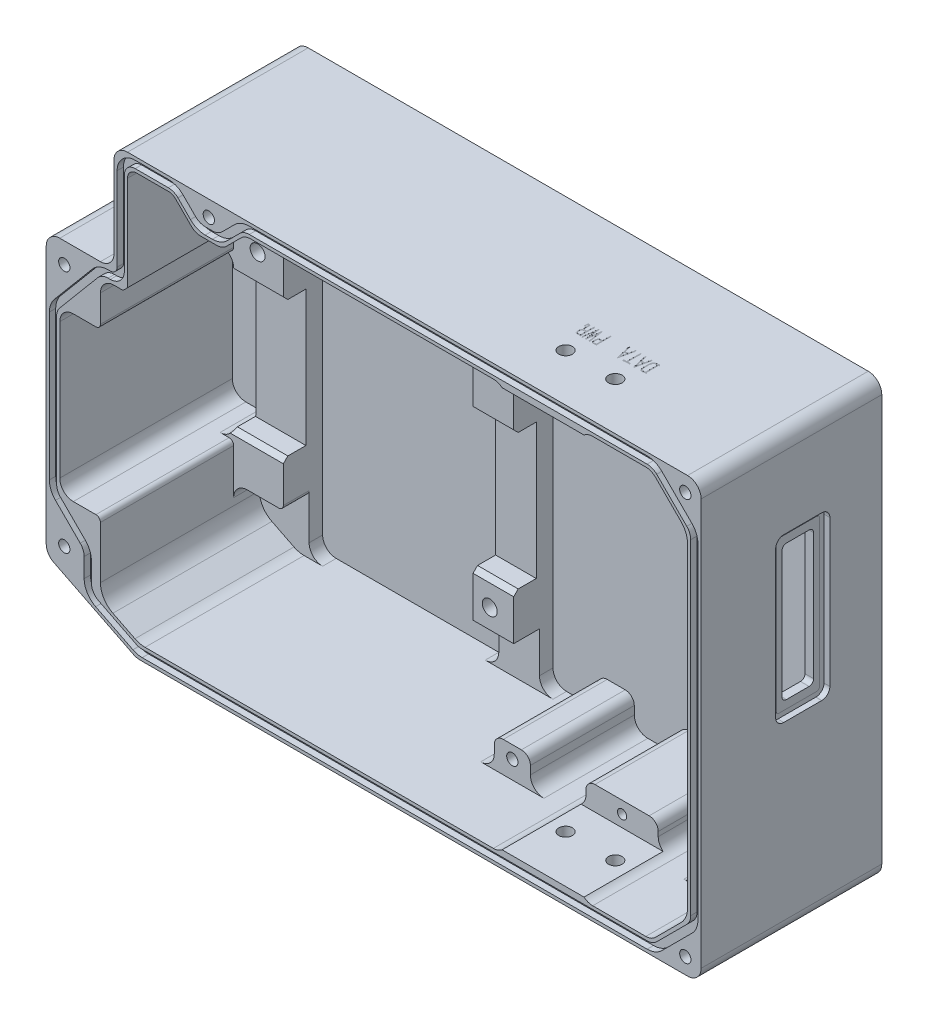
SolidWorks part; units mm, degrees
material "6061 合金"
ref_plane "前视基准面" through (0, 0, 0) normal (0, 0, 1) x (1, 0, 0)
ref_plane "上视基准面" through (0, 0, 0) normal (0, 1, 0) x (1, 0, 0)
ref_plane "右视基准面" through (0, 0, 0) normal (1, 0, 0) x (0, 0, -1)
sketch "草图1" plane through (0, 0, 0) normal (0, 0, 1) x (1, 0, 0)
  line L0 (15, 96) -> (15, 72)
  line L1 (20, 0) -> (145, 0)
  line L2 (0, 10) -> (0, 72)
  line L3 (15, 96) -> (145, 96)
  line L4 (145, 0) -> (145, 96)
  line L5 (0, 10) -> (20, 0)
  line L6 (15, 72) -> (0, 72)
  dimension "D1" = 125
  dimension "D2" = 96
  dimension "D3" = 130
  dimension "D4" = 10
  dimension "D5" = 24
  dimension "D6" = 145
extrude "凸台-拉伸1" add sketch "草图1" along normal blind 40
sketch "草图2" plane through (0, 0, 40) normal (0, 0, 1) x (1, 0, 0)
  line L5 (18, 93) -> (18, 69)
  line L6 (18, 93) -> (18, 69)
  line L8 (3, 69) -> (3, 11.8541)
  line L9 (20.7082, 3) -> (142, 3)
  line L10 (142, 3) -> (142, 93)
  line L11 (142, 93) -> (18, 93)
  line L12 (3, 69) -> (3, 11.8541)
  line L13 (20.7082, 3) -> (142, 3)
  line L14 (142, 3) -> (142, 93)
  line L15 (142, 93) -> (18, 93)
  line L16 (3, 11.8541) -> (20.7082, 3)
  line L17 (3, 11.8541) -> (20.7082, 3)
  line L19 (18, 69) -> (3, 69)
  line L20 (18, 69) -> (3, 69)
  dimension "D1" = 3
extrude "切除-拉伸1" cut sketch "草图2" against normal offset from surface (38.2 mm away) 1.8 up to face at (48.5714, 49.4286, 0)
sketch "草图74" plane through (0, 0, 1.8) normal (0, 0, 1) x (1, 0, 0)
  line L0 (18, 93) -> (18, 69) construction
  line L1 (18, 81) -> (74, 81)
  line L2 (18, 81) -> (18, 61)
  line L3 (18, 61) -> (74, 61)
  line L4 (74, 81) -> (74, 61)
  line L6 (145, 96) -> (15, 96) construction
  line L7 (145, 0) -> (145, 96) construction
  dimension "D1" = 15
  dimension "D2" = 20
  dimension "D3" = 71
extrude "凸台-拉伸25" add sketch "草图74" along normal blind 3
sketch "草图70" plane through (0, 0, 1.8) normal (0, 0, 1) x (1, 0, 0)
  line L1 (28, 93) -> (44, 93)
  line L5 (33, 88) -> (39, 88)
  line L6 (39, 88) -> (44, 93)
  line L7 (142, 93) -> (18, 93) construction
  line L8 (33, 88) -> (28, 93)
  line L9 (142, 93) -> (18, 93) construction
  line L10 (18, 93) -> (18, 81) construction
  dimension "D1" = 45
  dimension "D2" = 45
  dimension "D3" = 10
  dimension "D4" = 5
  dimension "D5" = 16
extrude "凸台-拉伸24" add sketch "草图70" along normal up to surface (38.2 mm away) up to face at (49.5297, 48.8363, 40)
sketch "草图39" plane through (0, 0, 1.8) normal (0, 0, 1) x (1, 0, 0)
  line L0 (134, 93) -> (142, 85)
  line L3 (142, 85) -> (142, 93)
  line L4 (142, 93) -> (134, 93)
  line L5 (134, 3) -> (142, 3)
  line L7 (142, 3) -> (142, 11)
  line L8 (142, 3) -> (142, 93) construction
  line L9 (142, 11) -> (134, 3)
  dimension "D1" = 8
  dimension "D2" = 8
  dimension "D3" = 8
  dimension "D4" = 8
extrude "凸台-拉伸9" add sketch "草图39" along normal up to surface (38.2 mm away) up to face at (44.6098, 63.9867, 40)
fillet "圆角66" radius 3 1 edges at (15, 72, 20)
fillet "圆角17" radius 3 2 edges at (145, 96, 20) (145, 0, 20)
sketch "草图17" plane through (145, 0, 0) normal (1, 0, 0) x (0, 0, -1)
  line L0 (-40, 3) -> (-40, 93) construction
  line L1 (-20, 74) -> (-15, 74)
  line L2 (-21, 73) -> (-21, 45)
  line L3 (-20, 44) -> (-15, 44)
  line L4 (-14, 73) -> (-14, 45)
  line L5 (-40, 96) -> (0, 96) construction
  arc A0 (-21, 45) -> (-20, 44) centre (-20, 45) ccw
  arc A1 (-15, 44) -> (-14, 45) centre (-15, 45) ccw
  arc A2 (-14, 73) -> (-15, 74) centre (-15, 73) ccw
  arc A3 (-21, 73) -> (-20, 74) centre (-20, 73) cw
  point P10 (-21, 44)
  point P15 (-14, 74)
  point P18 (-21, 74)
  dimension "D5" = 1
  dimension "D1" = 7
  dimension "D2" = 19
  dimension "D3" = 22
  dimension "D4" = 30
extrude "切除-拉伸2" cut sketch "草图17" against normal blind 10
sketch "草图18" plane through (0, 0, 0) normal (0, 0, -1) x (-1, 0, 0)
  line L0 (-142, 96) -> (-15, 96) construction
  line L1 (-63, 74) -> (-35, 74)
  line L2 (-64, 73) -> (-64, 68)
  line L3 (-63, 67) -> (-35, 67)
  line L4 (-34, 73) -> (-34, 68)
  line L5 (-145, 3) -> (-145, 93) construction
  arc A0 (-34, 73) -> (-35, 74) centre (-35, 73) ccw
  arc A1 (-34, 68) -> (-35, 67) centre (-35, 68) cw
  arc A2 (-64, 68) -> (-63, 67) centre (-63, 68) ccw
  arc A3 (-64, 73) -> (-63, 74) centre (-63, 73) cw
  point P10 (-34, 74)
  point P15 (-64, 67)
  point P18 (-64, 74)
  dimension "D5" = 1
  dimension "D1" = 7
  dimension "D2" = 30
  dimension "D3" = 22
  dimension "D4" = 81
extrude "切除-拉伸3" cut sketch "草图18" against normal blind 10
sketch "草图19" plane through (145, 0, 0) normal (1, 0, 0) x (0, 0, -1)
  line L5 (-21.7, 77) -> (-13.3, 77)
  line L6 (-23.5, 75.2) -> (-23.5, 42.8)
  line L7 (-21.7, 41) -> (-13.3, 41)
  line L8 (-11.5, 75.2) -> (-11.5, 42.8)
  line L10 (-21, 59) -> (-54.4631, 59) construction
  line L11 (-21, 73) -> (-21, 45) construction
  line L14 (-17.5, 44) -> (-17.5, 40.5608) construction
  line L15 (-20, 44) -> (-15, 44) construction
  arc A0 (-23.5, 42.8) -> (-21.7, 41) centre (-21.7, 42.8) ccw
  arc A1 (-11.5, 42.8) -> (-13.3, 41) centre (-13.3, 42.8) cw
  arc A2 (-11.5, 75.2) -> (-13.3, 77) centre (-13.3, 75.2) ccw
  arc A3 (-23.5, 75.2) -> (-21.7, 77) centre (-21.7, 75.2) cw
  point P3 (-23.5, 41)
  point P19 (-11.5, 77)
  point P22 (-23.5, 77)
  dimension "D3" = 1.8
  dimension "D1" = 36
  dimension "D2" = 12
extrude "切除-拉伸4" cut sketch "草图19" against normal blind 1.1
sketch "草图20" plane through (0, 0, 0) normal (0, 0, -1) x (-1, 0, 0)
  line L0 (-49, 74) -> (-49, 89.8189) construction
  line L1 (-65.2, 76.5) -> (-32.8, 76.5)
  line L2 (-67, 74.7) -> (-67, 66.3)
  line L3 (-65.2, 64.5) -> (-32.8, 64.5)
  line L4 (-31, 74.7) -> (-31, 66.3)
  line L5 (-35, 74) -> (-63, 74) construction
  line L6 (-64, 70.5) -> (-139.8388, 70.5) construction
  line L7 (-64, 73) -> (-64, 68) construction
  arc A0 (-32.8, 76.5) -> (-31, 74.7) centre (-32.8, 74.7) cw
  arc A1 (-32.8, 64.5) -> (-31, 66.3) centre (-32.8, 66.3) ccw
  arc A2 (-65.2, 64.5) -> (-67, 66.3) centre (-65.2, 66.3) cw
  arc A3 (-67, 74.7) -> (-65.2, 76.5) centre (-65.2, 74.7) cw
  point P14 (-31, 76.5)
  point P19 (-67, 64.5)
  point P22 (-67, 76.5)
  dimension "D3" = 1.8
  dimension "D1" = 36
  dimension "D2" = 12
extrude "切除-拉伸5" cut sketch "草图20" against normal blind 1.1
sketch "草图21" plane through (143.9, 0, 0) normal (1, 0, 0) x (0, 0, -1)
  line L4 (-21.7, 42.2) -> (-13.3, 42.2)
  line L5 (-12.7, 42.8) -> (-12.7, 75.2)
  line L6 (-13.3, 75.8) -> (-21.7, 75.8)
  line L7 (-22.3, 75.2) -> (-22.3, 42.8)
  line L8 (-21.7, 41) -> (-13.3, 41)
  line L9 (-11.5, 42.8) -> (-11.5, 75.2)
  line L10 (-13.3, 77) -> (-21.7, 77)
  line L11 (-23.5, 75.2) -> (-23.5, 42.8)
  line L12 (-21.7, 41) -> (-13.3, 41)
  line L13 (-11.5, 42.8) -> (-11.5, 75.2)
  line L14 (-13.3, 77) -> (-21.7, 77)
  line L15 (-23.5, 75.2) -> (-23.5, 42.8)
  arc A4 (-13.3, 42.2) -> (-12.7, 42.8) centre (-13.3, 42.8) ccw
  arc A5 (-12.7, 75.2) -> (-13.3, 75.8) centre (-13.3, 75.2) ccw
  arc A6 (-21.7, 75.8) -> (-22.3, 75.2) centre (-21.7, 75.2) ccw
  arc A7 (-22.3, 42.8) -> (-21.7, 42.2) centre (-21.7, 42.8) ccw
  arc A8 (-23.5, 42.8) -> (-21.7, 41) centre (-21.7, 42.8) ccw
  arc A9 (-13.3, 41) -> (-11.5, 42.8) centre (-13.3, 42.8) ccw
  arc A10 (-11.5, 75.2) -> (-13.3, 77) centre (-13.3, 75.2) ccw
  arc A11 (-21.7, 77) -> (-23.5, 75.2) centre (-21.7, 75.2) ccw
  arc A12 (-23.5, 42.8) -> (-21.7, 41) centre (-21.7, 42.8) ccw
  arc A13 (-13.3, 41) -> (-11.5, 42.8) centre (-13.3, 42.8) ccw
  arc A14 (-11.5, 75.2) -> (-13.3, 77) centre (-13.3, 75.2) ccw
  arc A15 (-21.7, 77) -> (-23.5, 75.2) centre (-21.7, 75.2) ccw
  dimension "D2" = 1.2
  dimension "D1" = 0
extrude "切除-拉伸9" cut sketch "草图21" against normal blind 0.2
sketch "草图14" plane through (0, 0, 1.8) normal (0, 0, 1) x (1, 0, 0)
  line L0 (3, 69) -> (3, 11.8541) construction
  line L2 (3, 69) -> (3, 59)
  line L3 (3, 59) -> (12, 59)
  line L4 (12, 69) -> (12, 59)
  line L5 (145, 41) -> (0, 41) construction
  line L6 (3, 23) -> (12, 23)
  line L7 (3, 23) -> (3, 11.8541)
  line L8 (3, 11.8541) -> (20.7082, 3) construction
  line L9 (12, 23) -> (12, 7.3541)
  line L11 (3, 69) -> (12, 69)
  line L12 (12, 7.3541) -> (3, 11.8541)
  line L13 (18, 69) -> (3, 69) construction
  line L14 (0, 72) -> (0, 10) construction
  dimension "D1" = 36
  dimension "D2" = 9
  dimension "D3" = 9
extrude "凸台-拉伸11" add sketch "草图14" along normal up to surface (38.2 mm away) up to face at (58.3622, 61.5272, 40)
hole_wizard "M4 螺纹孔1" positions "草图16" profile "草图15" tap size "M4" standard "Iso"
sketch "草图16" plane through (0, 0, 0) normal (-1, 0, 0) x (0, 0, 1)
  line L0 (0, 41) -> (58.2526, 41) construction
  line L1 (0, 72) -> (0, 10) construction
  line L2 (11.5, 63) -> (21.5, 63) construction
  line L4 (11.5, 19) -> (22.5, 19) construction
  point P0 (11.5, 63)
  point P2 (31.5, 63)
  point P4 (31.5, 19)
  point P6 (11.5, 19)
  point P25 (21.5, 63)
  point P27 (21.5, 19)
  dimension "D1" = 44
  dimension "D2" = 44
  dimension "D3" = 11.5
  dimension "D4" = 20
  dimension "D5" = 10
  dimension "D6" = 10
sketch "草图15" plane through (0, 63, 11.5) normal (0, 1, 0) x (0, 0, 1)
  line L0 (0, 0) -> (0, 11.0914)
  line L1 (0, 11.0914) -> (1.65, 10.1)
  line L2 (1.65, 10.1) -> (1.65, 0)
  line L5 (1.65, 0) -> (0, 0)
  line L10 (0, 11.0914) -> (-1.65, 10.1) construction
  line L11 (0, -6.35) -> (0, 107.95) construction
  dimension "螺纹孔钻头直径" = 3.3
  dimension "螺纹孔钻头深度" = 10.1
  dimension "导头角度" = 118
cosmetic thread "孔螺蚊线15" parameters "D1"=8, "D2"=4
cosmetic thread "孔螺蚊线16" parameters "D1"=8, "D2"=4
cosmetic thread "孔螺蚊线17" parameters "D1"=8, "D2"=4
cosmetic thread "孔螺蚊线18" parameters "D1"=8, "D2"=4
cosmetic thread "孔螺蚊线52" parameters "D1"=8, "D2"=4
cosmetic thread "孔螺蚊线53" parameters "D1"=8, "D2"=4
fillet "圆角27" radius 3 4 edges at (0, 10, 20) (15, 96, 20) (0, 72, 20) (20, 0, 20)
sketch "草图42" plane through (0, 0, 0) normal (-1, 0, 0) x (0, 0, 1)
  line L0 (21.5, 51) -> (21.5, 40.5248) construction
  line L1 (0, 69) -> (0, 11.8541) construction
  line L2 (21.5, 35) -> (21.5, 31) construction
  line L3 (26.5, 35) -> (26.5, 31)
  line L4 (16.5, 35) -> (16.5, 31)
  line L6 (0, 96) -> (40, 96) construction
  circle A0 centre (21.5, 51) radius 5
  arc A1 (26.5, 35) -> (16.5, 35) centre (21.5, 35) ccw
  arc A2 (16.5, 31) -> (26.5, 31) centre (21.5, 31) ccw
  point P7 (21.5, 33)
  dimension "D2" = 10
  dimension "D3" = 5
  dimension "D4" = 4
  dimension "D5" = 16
  dimension "D6" = 45
  dimension "D1" = 21.5
extrude "切除-拉伸16" cut sketch "草图42" against normal blind 2.3
sketch "草图46" plane through (15, -25, 0) normal (1, 0, 0) x (0, 1, 0)
  line L2 (121, 40) -> (121, 0) construction
  line L3 (118, 40) -> (100, 40) construction
  circle A0 centre (107, 22) radius 5.5
  dimension "D1" = 11
  dimension "D2" = 14
  dimension "D3" = 18
extrude "切除-拉伸18" cut sketch "草图46" along normal blind 10
fillet "圆角51" radius 5 2 edges at (142, 85, 20.9) (142, 11, 20.9)
sketch "草图47" plane through (0, 0, 1.8) normal (0, 0, 1) x (1, 0, 0)
  line L1 (84, 93) -> (92, 93)
  line L2 (84, 93) -> (84, 86.2)
  line L3 (84, 86.2) -> (92, 86.2)
  line L4 (92, 93) -> (92, 86.2)
  line L6 (129, 93) -> (142, 93)
  line L7 (129, 93) -> (129, 86.2)
  line L8 (129, 86.2) -> (142, 86.2)
  line L9 (142, 93) -> (142, 86.2)
  line L10 (145, 3) -> (145, 93) construction
  line L11 (134, 93) -> (44, 93) construction
  line L12 (134, 93) -> (44, 93) construction
  dimension "D1" = 8
  dimension "D2" = 13
  dimension "D3" = 6.8
  dimension "D4" = 6.8
  dimension "D5" = 45
  dimension "D6" = 3
extrude "凸台-拉伸10" add sketch "草图47" along normal blind 23
ref_plane "基准面1" through (0, 48, 0) normal (0, -1, 0) x (-1, 0, 0)
mirror "镜向1" about plane through (0, 48, 0) normal (0, -1, 0) of "凸台-拉伸10"
hole_wizard "M3 螺纹孔2" positions "草图49" profile "草图48" tap size "M3" standard "Iso"
sketch "草图49" plane through (0, 0, 24.8) normal (0, 0, 1) x (1, 0, 0)
  line L2 (145, 48) -> (-47.6545, 48) construction
  line L3 (145, 3) -> (145, 93) construction
  line L4 (-22, 48) -> (22, 48) construction
  line L8 (129, 93) -> (129, 86.2) construction
  point P0 (88, 89)
  point P2 (132, 89)
  point P4 (88, 7)
  point P6 (132, 7)
  dimension "D1" = 44
  dimension "D2" = 82
  dimension "D3" = 3
  dimension "D4" = 82
sketch "草图48" plane through (88, 89, 24.8) normal (1, 0, 0) x (0, -1, 0)
  line L0 (0, 0) -> (0, 8.2511)
  line L1 (0, 8.2511) -> (1.25, 7.5)
  line L2 (1.25, 7.5) -> (1.25, 0)
  line L5 (1.25, 0) -> (0, 0)
  line L10 (0, 8.2511) -> (-1.25, 7.5) construction
  line L11 (0, -6.35) -> (0, 107.95) construction
  dimension "螺纹孔钻头直径" = 2.5
  dimension "螺纹孔钻头深度" = 7.5
  dimension "导头角度" = 118
cosmetic thread "孔螺蚊线32" parameters "D1"=6, "D2"=3
cosmetic thread "孔螺蚊线34" parameters "D1"=6, "D2"=3
cosmetic thread "孔螺蚊线36" parameters "D1"=6, "D2"=3
cosmetic thread "孔螺蚊线37" parameters "D1"=6, "D2"=3
sketch "草图50" plane through (15, -25, 0) normal (1, 0, 0) x (0, 1, 0)
  circle A0 centre (107, 22) radius 6.5
  dimension "D1" = 13
extrude "切除-拉伸19" cut sketch "草图50" along normal blind 1
sketch "草图51" plane through (0, 0, 1.8) normal (0, 0, 1) x (1, 0, 0)
  line L0 (12, 69) -> (12, 15)
  line L1 (12, 15) -> (23, 15)
  line L2 (23, 15) -> (23, 69)
  line L3 (23, 69) -> (12, 69)
  line L4 (20.7082, 0) -> (142, 0) construction
  line L7 (65, 93) -> (74, 93)
  line L8 (65, 93) -> (65, 15)
  line L9 (65, 15) -> (74, 15)
  line L10 (74, 93) -> (74, 15)
  line L13 (84, 93) -> (44, 93) construction
  line L15 (18, 69) -> (12, 69) construction
  line L16 (134, 93) -> (44, 93) construction
  dimension "D1" = 15
  dimension "D2" = 74
  dimension "D3" = 51
  dimension "D4" = 15
  dimension "D6" = 9
extrude "凸台-拉伸12" add sketch "草图51" along normal blind 8.7
sketch "草图53" plane through (0, 0, 1.8) normal (0, 0, 1) x (1, 0, 0)
  line L0 (65, 15) -> (74, 15)
  line L1 (74, 15) -> (74, 3)
  line L2 (74, 3) -> (65, 3)
  line L3 (20.7082, 3) -> (84, 3) construction
  line L4 (65, 3) -> (65, 15)
  line L5 (12, 15) -> (23, 15)
  line L6 (23, 15) -> (23, 0.5)
  line L7 (23, 0.5) -> (12, 6)
  line L8 (12, 6) -> (12, 15)
  line L9 (12, 7.3541) -> (20.7082, 3) construction
  line L10 (20.7082, 3) -> (134, 3) construction
extrude "凸台-拉伸16" add sketch "草图53" along normal blind 3
hole_wizard "M4 螺纹孔2" positions "草图57" profile "草图55" tap size "M4" standard "Iso"
sketch "草图57" plane through (0, 0, 10.5) normal (0, 0, 1) x (1, 0, 0)
  point P0 (17.3, 61.7)
  point P3 (68.7, 19.3)
sketch "草图55" plane through (17.3, 61.7, 10.5) normal (1, 0, 0) x (0, -1, 0)
  line L0 (0, 0) -> (0, 9.9914)
  line L1 (0, 9.9914) -> (1.65, 9)
  line L2 (1.65, 9) -> (1.65, 0)
  line L5 (1.65, 0) -> (0, 0)
  line L10 (0, 9.9914) -> (-1.65, 9) construction
  line L11 (0, -6.35) -> (0, 107.95) construction
  dimension "螺纹孔钻头直径" = 3.3
  dimension "螺纹孔钻头深度" = 9
  dimension "导头角度" = 118
cosmetic thread "孔螺蚊线39" parameters "D1"=7, "D2"=4
cosmetic thread "孔螺蚊线44" parameters "D1"=7, "D2"=4
fillet "圆角39" radius 3 3 edges at (3, 23, 20.9) (3, 59, 20.9) (12, 69, 25.25)
fillet "圆角58" radius 2 2 edges at (18, 93, 20.9) (28, 93, 20.9)
hole_wizard "M3 螺纹孔4" positions "草图5" profile "草图4" tap size "M3" standard "Iso"
sketch "草图5" plane through (0, 0, 40) normal (0, 0, 1) x (1, 0, 0)
  line L0 (145, 3) -> (145, 93) construction
  line L1 (20.7082, 0) -> (142, 0) construction
  line L2 (142, 96) -> (18, 96) construction
  line L3 (0, 40.4271) -> (24.3232, 40.4271) construction
  line L4 (0, 69) -> (0, 11.8541) construction
  line L5 (0, 69) -> (0, 11.8541) construction
  point P0 (141.5, 92.5)
  point P2 (141.5, 3.5)
  point P22 (4, 67.4271)
  point P24 (4, 13.4271)
  dimension "D1" = 3.5
  dimension "D2" = 3.5
  dimension "D3" = 3.5
  dimension "D4" = 3.5
  dimension "D5" = 54
  dimension "D6" = 4
sketch "草图4" plane through (141.5, 92.5, 40) normal (1, 0, 0) x (0, -1, 0)
  line L0 (0, 0) -> (0, 9.2511)
  line L1 (0, 9.2511) -> (1.25, 8.5)
  line L2 (1.25, 8.5) -> (1.25, 0)
  line L5 (1.25, 0) -> (0, 0)
  line L10 (0, 9.2511) -> (-1.25, 8.5) construction
  line L11 (0, -6.35) -> (0, 107.95) construction
  dimension "螺纹孔钻头直径" = 2.5
  dimension "螺纹孔钻头深度" = 8.5
  dimension "导头角度" = 118
cosmetic thread "孔螺蚊线1" parameters "D1"=7, "D2"=3
cosmetic thread "孔螺蚊线2" parameters "D1"=7, "D2"=3
cosmetic thread "孔螺蚊线42" parameters "D1"=7, "D2"=3
cosmetic thread "孔螺蚊线47" parameters "D1"=7, "D2"=3
hole_wizard "M3 螺纹孔5" positions "草图68" profile "草图67" tap size "M3" standard "Iso"
sketch "草图68" plane through (0, 0, 40) normal (0, 0, 1) x (1, 0, 0)
  line L0 (142, 96) -> (18, 96) construction
  line L1 (15, 93) -> (15, 75) construction
  point P0 (36, 92.5)
  dimension "D1" = 3.5
  dimension "D2" = 21
sketch "草图67" plane through (36, 92.5, 40) normal (1, 0, 0) x (0, -1, 0)
  line L0 (0, 0) -> (0, 8.2511)
  line L1 (0, 8.2511) -> (1.25, 7.5)
  line L2 (1.25, 7.5) -> (1.25, 0)
  line L5 (1.25, 0) -> (0, 0)
  line L10 (0, 8.2511) -> (-1.25, 7.5) construction
  line L11 (0, -6.35) -> (0, 107.95) construction
  dimension "螺纹孔钻头直径" = 2.5
  dimension "螺纹孔钻头深度" = 7.5
  dimension "导头角度" = 118
cosmetic thread "孔螺蚊线48" parameters "D1"=6, "D2"=3
sketch "草图45" plane through (0, 0, 40) normal (0, 0, 1) x (1, 0, 0)
  line L0 (145, 48) -> (121.2232, 48) construction
  line L1 (145, 3) -> (145, 93) construction
  line L2 (142.7, 85.2899) -> (142.7, 10.7101)
  line L3 (142, 13.0711) -> (142, 82.9289) construction
  line L4 (142.7, 85.2899) -> (134.2899, 93.7)
  line L5 (134.2899, 93.7) -> (43.7101, 93.7)
  line L6 (134.9527, 95.3) -> (43.0473, 95.3)
  line L7 (142.7, 10.7101) -> (134.2899, 2.3)
  line L8 (134.2899, 2.3) -> (20.543, 2.3)
  line L9 (144.3, 85.9527) -> (134.9527, 95.3)
  line L11 (140.5355, 86.4645) -> (134, 93) construction
  line L13 (144.3, 85.9527) -> (144.3, 10.0473)
  line L14 (144.3, 10.0473) -> (134.9527, 0.7)
  line L15 (134.9527, 0.7) -> (20.1652, 0.7)
  line L16 (134.2899, 93.7) -> (68, 93.7) construction
  line L17 (134.9527, 95.3) -> (68, 95.3) construction
  line L18 (134.2899, 2.3) -> (35.5, 2.3) construction
  line L19 (43.7101, 93.7) -> (38.7101, 88.7)
  line L20 (38.7101, 88.7) -> (33.2899, 88.7)
  line L22 (17.3, 91.3) -> (17.3, 72.8)
  line L23 (14.2, 69.7) -> (12.3, 69.7)
  line L24 (2.3, 57.7825) -> (2.3, 23.2715)
  line L25 (2.3, 23.2715) -> (10, 15.5715)
  line L26 (10, 15.5715) -> (10, 7.5715)
  line L27 (15.7, 91.3) -> (15.7, 72.8)
  line L28 (14.2, 71.3) -> (11.5539, 71.3)
  line L29 (0.7, 58.3648) -> (0.7, 22.6087)
  line L30 (0.7, 22.6087) -> (8.4, 14.9087)
  line L31 (8.4, 14.9087) -> (8.4, 6.5826)
  line L32 (134.9527, 0.7) -> (35.5, 0.7) construction
  line L33 (20.543, 2.3) -> (10, 7.5715)
  line L34 (18, 91) -> (18, 69) construction
  line L35 (8.4, 6.5826) -> (20.1652, 0.7)
  line L36 (12, 7.3541) -> (20.7082, 3) construction
  line L38 (3, 56) -> (3, 26) construction
  line L39 (12, 7.3541) -> (12, 23) construction
  line L40 (65, 93) -> (44, 93) construction
  line L41 (33.2899, 88.7) -> (28.2899, 93.7)
  line L42 (28.2899, 93.7) -> (19.7, 93.7)
  line L43 (43.0473, 95.3) -> (38.0473, 90.3)
  line L44 (38.0473, 90.3) -> (33.9527, 90.3)
  line L45 (33.9527, 90.3) -> (28.9527, 95.3)
  line L46 (28.9527, 95.3) -> (19.7, 95.3)
  line L47 (44, 93) -> (39, 88) construction
  line L48 (39, 88) -> (33, 88) construction
  line L49 (33, 88) -> (28.5858, 92.4142) construction
  line L50 (27.1716, 93) -> (20, 93) construction
  line L51 (18, 69) -> (15, 69) construction
  line L52 (12.3, 69.7) -> (2.3, 57.7825)
  line L53 (11.5539, 71.3) -> (0.7, 58.3648)
  arc A0 (17.3, 91.3) -> (19.7, 93.7) centre (19.7, 91.3) cw
  arc A1 (15.7, 91.3) -> (19.7, 95.3) centre (19.7, 91.3) cw
  arc A2 (15.7, 72.8) -> (14.2, 71.3) centre (14.2, 72.8) cw
  arc A3 (14.2, 69.7) -> (17.3, 72.8) centre (14.2, 72.8) ccw
  point P47 (12, 15.1771)
  point P65 (16.5, 69)
  point P74 (17.3, 69.7)
  dimension "D25" = 2.4
  dimension "D26" = 4
  dimension "D31" = 1.5
  dimension "D32" = 3.1
  dimension "D1" = 0.7
  dimension "D2" = 0.7
  dimension "D3" = 0.7
  dimension "D4" = 0.7
  dimension "D5" = 1.6
  dimension "D7" = 1.6
  dimension "D8" = 1.6
  dimension "D9" = 1.6
  dimension "D10" = 1.6
  dimension "D11" = 1.6
  dimension "D12" = 0.7
  dimension "D13" = 0.7
  dimension "D14" = 1.6
  dimension "D15" = 0.7
  dimension "D16" = 0.7
  dimension "D17" = 2
  dimension "D18" = 135
  dimension "D19" = 8
  dimension "D20" = 1.6
  dimension "D21" = 0.7
  dimension "D22" = 1.6
  dimension "D23" = 0.7
  dimension "D24" = 1.6
  dimension "D27" = 0.7
  dimension "D28" = 5
  dimension "D29" = 1.6
  dimension "D30" = 130
  dimension "D6" = 1.6
extrude "切除-拉伸17" cut sketch "草图45" against normal blind 1.4
sketch "草图61" plane through (0, 0, 1.8) normal (0, 0, 1) x (1, 0, 0)
  line L0 (92, 3) -> (129, 3) construction
  line L1 (102, 3) -> (118, 3)
  line L2 (102, 3) -> (102, 3.7)
  line L3 (102, 3.7) -> (118, 3.7)
  line L4 (118, 3) -> (118, 3.7)
  line L5 (145, 3) -> (145, 93) construction
  dimension "D1" = 0.7
  dimension "D2" = 16
  dimension "D3" = 27
extrude "凸台-拉伸18" add sketch "草图61" along normal up to surface (38.2 mm away) up to face at (48.3758, 57.831, 40)
sketch "草图60" plane through (0, 0, 0) normal (0, -1, 0) x (1, 0, 0)
  line L0 (104.5, 29.5) -> (115.5, 29.5) construction
  line L1 (20.7082, 40) -> (142, 40) construction
  line L3 (118, 40) -> (118, 1.8) construction
  circle A0 centre (104.5, 29.5) radius 1.5
  circle A1 centre (115.5, 29.5) radius 1.5
  dimension "D1" = 3
  dimension "D3" = 2.5
  dimension "D2" = 10.5
  dimension "D4" = 11
extrude "切除-拉伸20" cut sketch "草图60" against normal blind 10
sketch "草图62" plane through (0, 0, 1.8) normal (0, 0, 1) x (1, 0, 0)
  line L1 (102, 3.7) -> (118, 3.7)
  line L2 (102, 3.7) -> (102, 9)
  line L3 (102, 9) -> (118, 9)
  line L4 (118, 3.7) -> (118, 9)
  dimension "D1" = 5.3
extrude "凸台-拉伸19" add sketch "草图62" along normal blind 20.7
mirror "镜向3" about plane through (0, 48, 0) normal (0, -1, 0) of "凸台-拉伸19", "切除-拉伸20", "凸台-拉伸18"
fillet "圆角40" radius 3 8 edges at (129, 93, 13.3) (92, 93, 13.3) (92, 3, 13.3) (102, 3, 20.9) (118, 3, 20.9) (129, 3, 13.3) (118, 93, 20.9) (102, 93, 20.9)
fillet "圆角44" radius 3 4 edges at (84, 93, 13.3) (39, 88, 20.9) (33, 88, 20.9) (44, 93, 20.9)
fillet "圆角45" radius 5 2 edges at (20.7082, 3, 22.4) (12, 7.3541, 22.4)
fillet "圆角46" radius 3 2 edges at (12, 23, 6.15) (12, 59, 6.15)
fillet "圆角48" radius 2 10 edges at (129, 9.8, 13.3) (118, 9, 12.15) (102, 9, 12.15) (84, 9.8, 13.3) (92, 9.8, 13.3) (92, 86.2, 13.3) (84, 86.2, 13.3) (129, 86.2, 13.3) (118, 87, 12.15) (102, 87, 12.15)
fillet "圆角53" radius 3 2 edges at (140.7815, 86.2, 13.3) (140.7815, 9.8, 13.3)
fillet "圆角54" radius 3 2 edges at (134, 3, 32.4) (134, 93, 32.4)
fillet "圆角55" radius 3 14 edges at (142.7, 10.7101, 39.3) (134.2899, 2.3, 39.3) (20.543, 2.3, 39.3) (10, 7.5715, 39.3) (2.3, 23.2715, 39.3) (134.2899, 93.7, 39.3) (142.7, 85.2899, 39.3) (8.4, 14.9087, 39.3) (43.7101, 93.7, 39.3) (28.2899, 93.7, 39.3) (38.0473, 90.3, 39.3) (33.9527, 90.3, 39.3) (12.3, 69.7, 39.3) (2.3, 57.7825, 39.3)
fillet "圆角56" radius 4.6 14 edges at (134.9527, 95.3, 39.3) (144.3, 85.9527, 39.3) (144.3, 10.0473, 39.3) (134.9527, 0.7, 39.3) (20.1652, 0.7, 39.3) (8.4, 6.5826, 39.3) (10, 15.5715, 39.3) (0.7, 22.6087, 39.3) (43.0473, 95.3, 39.3) (28.9527, 95.3, 39.3) (11.5539, 71.3, 39.3) (0.7, 58.3648, 39.3) (38.7101, 88.7, 39.3) (33.2899, 88.7, 39.3)
sketch "草图65" plane through (0, 0, 1.8) normal (0, 0, 1) x (1, 0, 0)
  line L0 (18, 91) -> (18, 69) construction
  line L1 (18, 75) -> (33, 75)
  line L2 (18, 75) -> (18, 67)
  line L3 (18, 67) -> (33, 67)
  line L4 (33, 75) -> (33, 67)
  line L5 (142, 96) -> (18, 96) construction
  dimension "D1" = 8
  dimension "D2" = 21
  dimension "D3" = 15
extrude "凸台-拉伸22" add sketch "草图65" along normal up to surface (8.7 mm away) up to face at (70.35, 19.3, 10.5)
chamfer "倒角2" distance 1 angle 45 1 edges at (18, 69, 25.25)
hole_wizard "M3 螺纹孔6" positions "草图72" profile "草图71" tap size "M3" standard "Iso"
sketch "草图72" plane through (0, 0, 10.5) normal (0, 0, 1) x (1, 0, 0)
  point P0 (69, 71)
  point P3 (27, 71)
sketch "草图71" plane through (69, 71, 10.5) normal (1, 0, 0) x (0, -1, 0)
  line L0 (0, 0) -> (0, 8.7511)
  line L1 (0, 8.7511) -> (1.25, 8)
  line L2 (1.25, 8) -> (1.25, 0)
  line L5 (1.25, 0) -> (0, 0)
  line L10 (0, 8.7511) -> (-1.25, 8) construction
  line L11 (0, -6.35) -> (0, 107.95) construction
  dimension "螺纹孔钻头直径" = 2.5
  dimension "螺纹孔钻头深度" = 8
  dimension "导头角度" = 118
cosmetic thread "孔螺蚊线49" parameters "D1"=6.5, "D2"=3
cosmetic thread "孔螺蚊线50" parameters "D1"=6.5, "D2"=3
fillet "圆角59" radius 3 6 edges at (23, 67, 7.65) (18, 75, 7.65) (18, 81, 3.3) (65, 81, 3.3) (65, 61, 3.3) (23, 61, 3.3)
fillet "圆角60" radius 1 3 edges at (33, 75, 7.65) (33, 67, 7.65) (23, 15, 7.65)
fillet "圆角61" radius 3 5 edges at (74, 3, 3.3) (65, 3, 3.3) (23, 3, 3.3) (65, 93, 6.15) (74, 93, 6.15)
fillet "圆角62" radius 3 1 edges at (84, 3, 13.3)
fillet "圆角63" radius 1 2 edges at (12, 23, 25.25) (12, 59, 25.25)
sketch "草图75" plane through (0, 0, 1.1) normal (0, 0, -1) x (-1, 0, 0)
  line L0 (-32.8, 75) -> (-65.2, 75)
  line L1 (-65.5, 74.7) -> (-65.5, 66.3)
  line L2 (-65.2, 66) -> (-32.8, 66)
  line L3 (-32.5, 66.3) -> (-32.5, 74.7)
  line L4 (-32.8, 76.5) -> (-65.2, 76.5)
  line L5 (-67, 74.7) -> (-67, 66.3)
  line L6 (-65.2, 64.5) -> (-32.8, 64.5)
  line L7 (-31, 66.3) -> (-31, 74.7)
  line L8 (-32.8, 76.5) -> (-65.2, 76.5)
  line L9 (-67, 74.7) -> (-67, 66.3)
  line L10 (-65.2, 64.5) -> (-32.8, 64.5)
  line L11 (-31, 66.3) -> (-31, 74.7)
  arc A0 (-65.2, 75) -> (-65.5, 74.7) centre (-65.2, 74.7) ccw
  arc A1 (-65.5, 66.3) -> (-65.2, 66) centre (-65.2, 66.3) ccw
  arc A2 (-32.8, 66) -> (-32.5, 66.3) centre (-32.8, 66.3) ccw
  arc A3 (-32.5, 74.7) -> (-32.8, 75) centre (-32.8, 74.7) ccw
  arc A4 (-31, 74.7) -> (-32.8, 76.5) centre (-32.8, 74.7) ccw
  arc A5 (-65.2, 76.5) -> (-67, 74.7) centre (-65.2, 74.7) ccw
  arc A6 (-67, 66.3) -> (-65.2, 64.5) centre (-65.2, 66.3) ccw
  arc A7 (-32.8, 64.5) -> (-31, 66.3) centre (-32.8, 66.3) ccw
  arc A8 (-31, 74.7) -> (-32.8, 76.5) centre (-32.8, 74.7) ccw
  arc A9 (-65.2, 76.5) -> (-67, 74.7) centre (-65.2, 74.7) ccw
  arc A10 (-67, 66.3) -> (-65.2, 64.5) centre (-65.2, 66.3) ccw
  arc A11 (-32.8, 64.5) -> (-31, 66.3) centre (-32.8, 66.3) ccw
  dimension "D1" = 0
  dimension "D2" = 1.5
extrude "切除-拉伸21" cut sketch "草图75" against normal blind 0.2
sketch "草图77" plane through (0, 0, 0) normal (0, -1, 0) x (1, 0, 0)
  text T0 "S1    S2"
extrude "切除-拉伸23" cut sketch "草图77" against normal blind 0.01
hole_wizard "M2.5 螺纹孔1" positions "草图79" profile "草图78" tap size "M2.5" standard "Iso"
sketch "草图79" plane through (0, 0, 22.5) normal (0, 0, 1) x (1, 0, 0)
  point P0 (110, 6.3)
  point P4 (110, 89.7)
sketch "草图78" plane through (110, 6.3, 22.5) normal (1, 0, 0) x (0, -1, 0)
  line L0 (0, 0) -> (0, 6.9659)
  line L1 (0, 6.9659) -> (1.025, 6.35)
  line L2 (1.025, 6.35) -> (1.025, 0)
  line L5 (1.025, 0) -> (0, 0)
  line L10 (0, 6.9659) -> (-1.025, 6.35) construction
  line L11 (0, -6.35) -> (0, 107.95) construction
  dimension "螺纹孔钻头直径" = 2.05
  dimension "螺纹孔钻头深度" = 6.35
  dimension "导头角度" = 118
cosmetic thread "孔螺蚊线51" parameters "D1"=5, "D2"=2.5
cosmetic thread "孔螺蚊线54" parameters "D1"=5, "D2"=2.5
sketch "草图80" plane through (0, 0, 1.8) normal (0, 0, 1) x (1, 0, 0)
  circle A0 centre (91.8, 78.7) radius 6
  circle A1 centre (134.2, 27.3) radius 6
  dimension "D1" = 12
  dimension "D2" = 12
extrude "切除-拉伸24" cut sketch "草图80" against normal blind 1
sketch "草图81" plane through (0, 0, 10.5) normal (0, 0, 1) x (1, 0, 0)
  line L0 (65, 15) -> (74, 15) construction
  line L1 (7.3345, 55) -> (81.4222, 55)
  line L2 (7.3345, 55) -> (7.3345, 25)
  line L3 (7.3345, 25) -> (81.4222, 25)
  line L4 (81.4222, 55) -> (81.4222, 25)
  dimension "D1" = 10
  dimension "D2" = 30
extrude "切除-拉伸25" cut sketch "草图81" against normal blind 5
chamfer "倒角3" distance 1 angle 45 4 edges at (69.5, 25, 10.5) (69.5, 55, 10.5) (17.5, 55, 10.5) (17.4142, 25, 10.5)
sketch "草图82" plane through (0, 96, 0) normal (0, 1, 0) x (1, 0, 0)
  line L0 (118, -21.6) -> (97.7935, -21.6) construction
  line L1 (142, 0) -> (18, 0) construction
  line L2 (145, 0) -> (145, -40) construction
  text T0 "DATA  PWR   "
  dimension "D1" = 21.6
  dimension "D2" = 27
extrude "切除-拉伸26" cut sketch "草图82" against normal blind 0.01
fillet "圆角64" radius 3 1 edges at (12, 15, 7.65)
